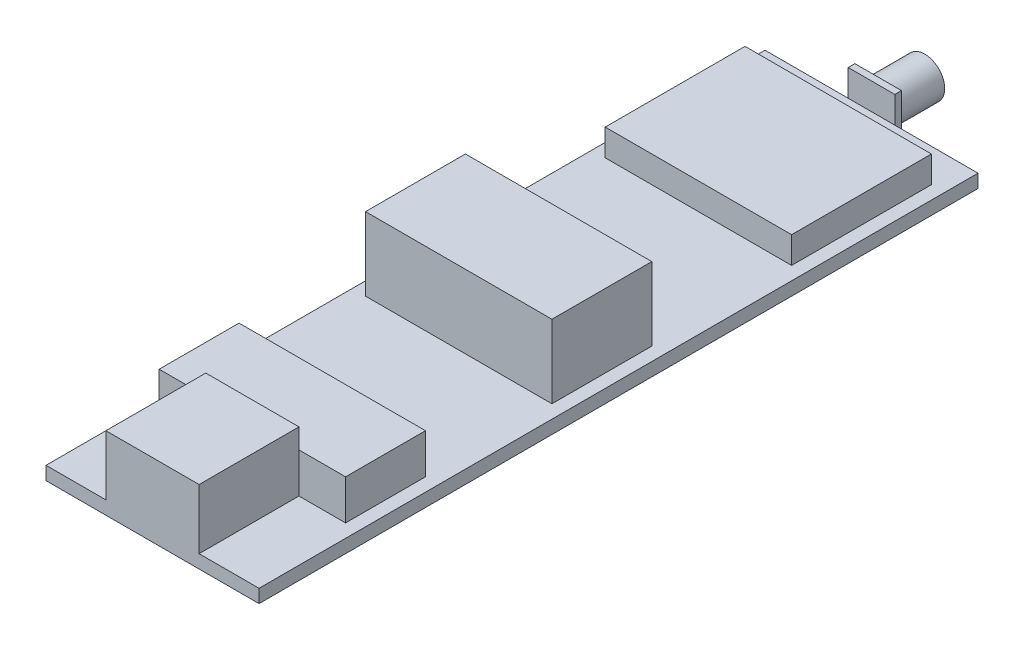
SolidWorks part; units mm, degrees
ref_plane "Спереди" through (0, 0, 0) normal (0, 0, 1) x (1, 0, 0)
ref_plane "Сверху" through (0, 0, 0) normal (0, 1, 0) x (1, 0, 0)
ref_plane "Справа" through (0, 0, 0) normal (1, 0, 0) x (0, 0, -1)
sketch "Эскиз1" plane through (0, 0, 0) normal (0, 1, 0) x (1, 0, 0)
  line L0 (0, 54) -> (0, -54) construction
  line L1 (-16, 54) -> (16, 54)
  line L2 (-16, 54) -> (-16, -54)
  line L3 (-16, -54) -> (16, -54)
  line L4 (16, 54) -> (16, -54)
  line L6 (-16, 0) -> (16, 0) construction
  point P6 (0, 0)
  dimension "D1" = 32
  dimension "D2" = 108
extrude "плата" add sketch "Эскиз1" along normal blind 2
sketch "Эскиз2" plane through (0, 2, 0) normal (0, 1, 0) x (1, 0, 0)
  line L0 (0, 54) -> (0, -54) construction
  line L1 (16, 54) -> (-16, 54) construction
  line L2 (-16, -54) -> (16, -54) construction
  line L3 (-16, 54) -> (-16, -54) construction
  line L4 (-7, -54) -> (7, -54)
  line L5 (-7, -54) -> (-7, -39)
  line L6 (-7, -39) -> (7, -39)
  line L7 (7, -54) -> (7, -39)
  line L8 (-14, -39) -> (14, -39)
  line L9 (-14, -39) -> (-14, -27)
  line L10 (-14, -27) -> (14, -27)
  line L11 (14, -39) -> (14, -27)
  line L13 (-14, -8) -> (14, -8)
  line L14 (-14, -8) -> (-14, 7)
  line L15 (-14, 7) -> (14, 7)
  line L16 (14, -8) -> (14, 7)
  line L17 (-14, 28) -> (14, 28)
  line L18 (-14, 28) -> (-14, 49)
  line L19 (-14, 49) -> (14, 49)
  line L20 (14, 28) -> (14, 49)
  point P10 (0, -39)
  point P15 (0, 7)
  point P16 (0, 49)
  point P18 (0, -27)
  dimension "D1" = 14
  dimension "D2" = 15
  dimension "D3" = 2
  dimension "D4" = 12
  dimension "D5" = 19
  dimension "D6" = 15
  dimension "D7" = 21
  dimension "D8" = 21
sketch "Эскиз3" plane through (0, 2, 0) normal (0, 1, 0) x (1, 0, 0)
  line L1 (-7, -54) -> (7, -54)
  line L2 (-7, -54) -> (-7, -39)
  line L3 (-7, -39) -> (7, -39)
  line L4 (7, -54) -> (7, -39)
extrude "ethernet" add sketch "Эскиз3" along normal blind 9
sketch "Эскиз4" plane through (0, 2, 0) normal (0, 1, 0) x (1, 0, 0)
  line L1 (-14, -39) -> (14, -39)
  line L2 (-14, -39) -> (-14, -27)
  line L3 (-14, -27) -> (14, -27)
  line L4 (14, -39) -> (14, -27)
extrude "микрухи" add sketch "Эскиз4" along normal blind 6
sketch "Эскиз5" plane through (0, 2, 0) normal (0, 1, 0) x (1, 0, 0)
  line L1 (-14, -8) -> (14, -8)
  line L2 (-14, -8) -> (-14, 7)
  line L3 (-14, 7) -> (14, 7)
  line L4 (14, -8) -> (14, 7)
extrude "радиатор" add sketch "Эскиз5" along normal blind 11
sketch "Эскиз6" plane through (0, 2, 0) normal (0, 1, 0) x (1, 0, 0)
  line L1 (-14, 28) -> (14, 28)
  line L2 (-14, 28) -> (-14, 49)
  line L3 (-14, 49) -> (14, 49)
  line L4 (14, 28) -> (14, 49)
extrude "антенна вифи" add sketch "Эскиз6" along normal blind 4
sketch "Эскиз7" plane through (0, 0, -54) normal (0, 0, -1) x (-1, 0, 0)
  line L0 (-16, 0) -> (16, 0) construction
  line L1 (-3.5, 6) -> (3.5, 6)
  line L2 (-3.5, 6) -> (-3.5, -1)
  line L3 (-3.5, -1) -> (3.5, -1)
  line L4 (3.5, 6) -> (3.5, -1)
  point P4 (0, -1)
  dimension "D1" = 7
  dimension "D2" = 7
  dimension "D3" = 1
extrude "основание sma" add sketch "Эскиз7" along normal blind 1
sketch "Эскиз8" plane through (0, 0, -55) normal (0, 0, -1) x (-1, 0, 0)
  line L0 (0, 6) -> (0, -1) construction
  line L1 (3.5, 6) -> (-3.5, 6) construction
  line L2 (-3.5, -1) -> (3.5, -1) construction
  line L4 (-3.5, 6) -> (-3.5, -1) construction
  line L5 (-3.5, 2.5) -> (3.5, 2.5) construction
  line L6 (3.5, -1) -> (3.5, 6) construction
  circle A0 centre (0, 2.5) radius 3
  dimension "D1" = 6
extrude "sma" add sketch "Эскиз8" along normal blind 7
